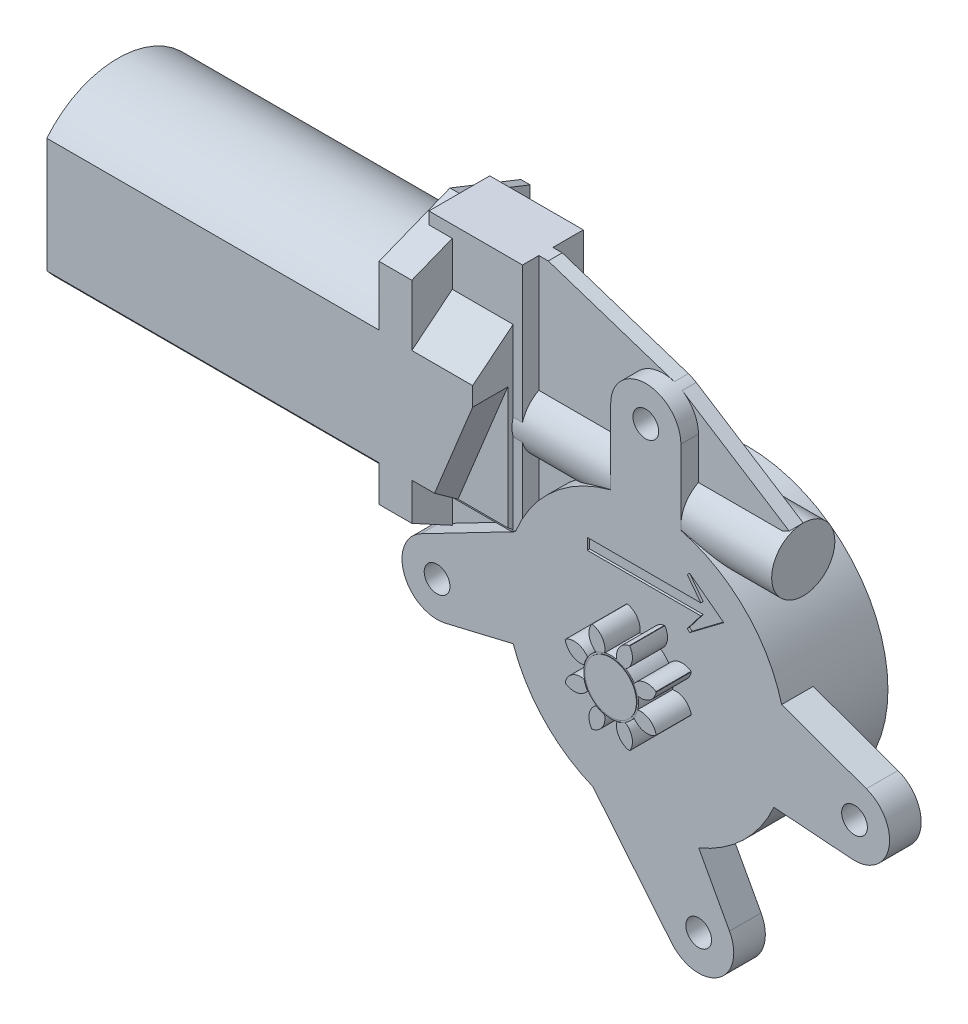
SolidWorks part; units mm, degrees
ref_plane "正面" through (0, 0, 0) normal (0, 0, 1) x (1, 0, 0)
ref_plane "平面" through (0, 0, 0) normal (0, 1, 0) x (1, 0, 0)
ref_plane "右側面" through (0, 0, 0) normal (1, 0, 0) x (0, 0, -1)
sketch "ｽｹｯﾁ2" plane through (0, 0, 0) normal (1, 0, 0) x (0, 0, -1)
  line L0 (0, 0) -> (0, 50000) construction
  line L1 (15.15, 12.2771) -> (15.15, -12.2771)
  line L2 (-15.15, 12.2771) -> (-15.15, -12.2771)
  arc A0 (-15.15, -12.2771) -> (15.15, -12.2771) centre (0, 0) ccw
  arc A2 (15.15, 12.2771) -> (-15.15, 12.2771) centre (0, 0) ccw
  dimension "D1" = 39
  dimension "D2" = 30.3
extrude "ﾎﾞｽ - 押し出し1" add sketch "ｽｹｯﾁ2" against normal blind 71
sketch "ｽｹｯﾁ3" plane through (-71, 0, 0) normal (-1, 0, 0) x (0, 0, 1)
  circle A0 centre (0, 0) radius 7
  dimension "D1" = 14
extrude "ﾎﾞｽ - 押し出し2" add sketch "ｽｹｯﾁ3" along normal blind 0.8
sketch "ｽｹｯﾁ4" plane through (-71.8, 0, 0) normal (-1, 0, 0) x (0, 0, 1)
  circle A0 centre (0, 0) radius 2.25
  dimension "D1" = 4.5
extrude "ﾎﾞｽ - 押し出し3" add sketch "ｽｹｯﾁ4" along normal blind 0.2
sketch "ｽｹｯﾁ5" plane through (0, 0, 0) normal (1, 0, 0) x (0, 0, -1)
  line L0 (0, 0) -> (0, 50000) construction
  line L1 (0, 0) -> (-50000, 0) construction
  line L2 (-15.15, 25) -> (-15.15, -20)
  line L3 (-15.15, -20) -> (5.15, -31)
  line L4 (5.15, -31) -> (15.15, -31)
  line L5 (15.15, -31) -> (15.15, 25)
  line L6 (15.15, 25) -> (0, 31)
  line L7 (0, 31) -> (-15.15, 25)
  line L8 (15.15, -12.2771) -> (15.15, 12.2771) construction
  line L9 (-15.15, 12.2771) -> (-15.15, -12.2771) construction
  circle A0 centre (0, 0) radius 26 construction
  circle A1 centre (0, 26) radius 2.5
  circle A2 centre (-10, 24) radius 2
  circle A3 centre (10, 24) radius 2
  circle A4 centre (7, -25.04) radius 2
  dimension "D6" = 52
  dimension "D8" = 5
  dimension "D9" = 4
  dimension "D10" = 7
  dimension "D11" = 4
  dimension "D2" = 31
  dimension "D3" = 25
  dimension "D4" = 62
  dimension "D5" = 20
  dimension "D7" = 10
  dimension "D12" = 10
extrude "ﾎﾞｽ - 押し出し4" add sketch "ｽｹｯﾁ5" along normal blind 2
sketch "ｽｹｯﾁ7" plane through (2, 0, 0) normal (1, 0, 0) x (0, 0, -1)
  circle A0 centre (0, 0) radius 6.75
  dimension "D1" = 13.5
extrude "ﾎﾞｽ - 押し出し7" add sketch "ｽｹｯﾁ7" along normal blind 73.5
sketch "ｽｹｯﾁ6" plane through (0, 0, 0) normal (0, 0, 1) x (1, 0, 0)
  line L0 (0, 0) -> (-50000, 0) construction
  line L1 (29.7505, -30) -> (-49970.2495, -30) construction
  line L2 (48.6, -30) -> (48.6, 49970) construction
  line L3 (2, 25) -> (2, -20) construction
  circle A0 centre (48.6, -30) radius 30
  dimension "D1" = 30
  dimension "D2" = 46.6
extrude "ﾎﾞｽ - 押し出し8" add sketch "ｽｹｯﾁ6" against normal blind 15
sketch "ｽｹｯﾁ8" plane through (0, 0, 0) normal (0, 0, 1) x (1, 0, 0)
  line L0 (48.6, -30) -> (48.6, 49970) construction
  line L1 (48.6, -30) -> (-49951.4, -30) construction
  line L2 (48.6, -36) -> (-49951.4, -36) construction
  line L3 (59.9, -30) -> (59.9, 49970) construction
  line L4 (54.1031, -78.2588) -> (37.3, -57.7905)
  line L5 (66.4901, -69.9194) -> (59.9, -57.7905)
  line L6 (92.6469, -43.4796) -> (75.9861, -42.2476)
  line L7 (95.741, -28.9436) -> (77.6268, -22.4207)
  line L8 (41.1, 15) -> (41.1, -0.9526)
  line L9 (56.1, 15) -> (56.1, -0.9526)
  line L10 (0.5475, -29.3419) -> (20.7407, -18.8709)
  line L11 (5.7319, -43.2973) -> (20.2627, -39.8487)
  arc A0 (41.1, -0.9526) -> (20.7407, -18.8709) centre (48.6, -30) ccw
  circle A1 centre (48.6, 15) radius 2.75
  circle A2 centre (4, -36) radius 2.75
  circle A3 centre (93.2, -36) radius 2.75
  circle A4 centre (59.9, -73.5) radius 2.75
  arc A5 (0.5475, -29.3419) -> (5.7319, -43.2973) centre (4, -36) ccw
  arc A6 (56.1, 15) -> (41.1, 15) centre (48.6, 15) ccw
  arc A7 (92.6469, -43.4796) -> (95.741, -28.9436) centre (93.2, -36) ccw
  arc A8 (54.1031, -78.2588) -> (66.4901, -69.9194) centre (59.9, -73.5) ccw
  arc A9 (29.6412, -6.75) -> (67.5588, -6.75) centre (48.6, -30) ccw construction
  arc A10 (59.9, -57.7905) -> (75.9861, -42.2476) centre (48.6, -30) ccw
  arc A11 (20.2627, -39.8487) -> (37.3, -57.7905) centre (48.6, -30) ccw
  arc A12 (77.6268, -22.4207) -> (56.1, -0.9526) centre (48.6, -30) ccw
  dimension "D3" = 60
  dimension "D4" = 43.5
  dimension "D5" = 44.6
  dimension "D6" = 44.6
  dimension "D8" = 5.5
  dimension "D9" = 15
  dimension "D1" = 11.3
  dimension "D2" = 6
  dimension "D7" = 45
extrude "ﾎﾞｽ - 押し出し9" add sketch "ｽｹｯﾁ8" along normal blind 6.75
sketch "ｽｹｯﾁ9" plane through (0, 0, 0) normal (0, 0, 1) x (1, 0, 0)
  line L0 (75.5, 6.75) -> (52.6308, 21.3247)
  line L1 (50.9466, 22.1235) -> (24, 31)
  line L2 (24, 31) -> (2, 31)
  line L3 (2, 31) -> (2, -28.5887)
  line L4 (20.7407, -18.8709) -> (0.5475, -29.3419) construction
  line L5 (2, -20) -> (2, -31) construction
  line L6 (2, -28.5887) -> (75.5, 6.75)
  arc A0 (56.1, 15) -> (41.1, 15) centre (48.6, 15) ccw construction
  arc A1 (50.9466, 22.1235) -> (52.6308, 21.3247) centre (48.6, 15) cw
  circle A2 centre (48.6, 15) radius 2.75
  dimension "D2" = 5.5
  dimension "D1" = 22
extrude "ﾎﾞｽ - 押し出し10" add sketch "ｽｹｯﾁ9" along normal blind 3 contours A1 L1 L2 L3 L6 L0 region at (28.0225, 5.7047, 0)
sketch "ｽｹｯﾁ10" plane through (0, 0, 0) normal (0, 0, 1) x (1, 0, 0)
  line L0 (2, 31) -> (22, 31)
  line L1 (24, 31) -> (2, 31) construction
  line L2 (22, 31) -> (22, -19.5)
  line L3 (22, -19.5) -> (2, -19.5)
  line L4 (2, 25) -> (2, -20) construction
  line L5 (2, -6.0467) -> (2, -26.5837) construction
  line L6 (-71, -19.5) -> (0, -19.5) construction
  line L7 (2, 31) -> (2, -19.5)
  dimension "D1" = 20
extrude "ﾎﾞｽ - 押し出し11" add sketch "ｽｹｯﾁ10" against normal blind 6.5 and the other way blind 6.5
sketch "ｽｹｯﾁ12" plane through (2, 0, 0) normal (1, 0, 0) x (0, 0, -1)
  line L0 (0, 0) -> (-50000, 0) construction
  line L1 (-15.15, 12) -> (-6.5, 19)
  line L2 (-15.15, 25) -> (-15.15, -20) construction
  line L4 (-6.5, 28.4257) -> (-6.5, 1.82) construction
  line L5 (-15.15, 12) -> (-15.15, -12)
  line L6 (-15.15, -12) -> (-6.5, -19)
  line L7 (-6.5, 19) -> (-6.5, -19)
  arc A0 (-6.5, 1.82) -> (-6.5, -1.82) centre (0, 0) ccw construction
  point P15 (-15.15, 0)
  point P16 (-6.75, 0)
  dimension "D1" = 24
  dimension "D2" = 38
extrude "ﾎﾞｽ - 押し出し19" add sketch "ｽｹｯﾁ12" along normal blind 18
sketch "ｽｹｯﾁ13" plane through (0, 0, 6.75) normal (0, 0, 1) x (1, 0, 0)
  circle A0 centre (48.6, -30) radius 10.5
  dimension "D1" = 21
extrude "ﾎﾞｽ - 押し出し20" add sketch "ｽｹｯﾁ13" along normal blind 7.5
sketch "ｽｹｯﾁ14" plane through (0, 0, 14.25) normal (0, 0, 1) x (1, 0, 0)
  circle A0 centre (48.6, -30) radius 5.85
  circle A1 centre (48.6, -30) radius 5.5
  dimension "D1" = 11
  dimension "D2" = 11.7
extrude "ｶｯﾄ - 押し出し1" cut sketch "ｽｹｯﾁ14" against normal blind 0.1
sketch "ｽｹｯﾁ15" plane through (0, 0, 15.15) normal (0, 0, 1) x (1, 0, 0)
  line L0 (0, 0) -> (-50000, 0) construction
  line L1 (2, 13.5772) -> (2, 50013.5772) construction
  line L3 (20, 8) -> (9, -19)
  line L4 (20, 1.82) -> (20, 19) construction
  line L5 (20, -19) -> (2, -19) construction
  line L6 (9, -19) -> (20, -19)
  line L7 (20, -19) -> (20, 8)
  dimension "D1" = 27
  dimension "D2" = 11
extrude "ｶｯﾄ - 押し出し2" cut sketch "ｽｹｯﾁ15" against normal blind 7.5
sketch "ｽｹｯﾁ16" plane through (2, 0, 0) normal (1, 0, 0) x (0, 0, -1)
  line L0 (-6.5, 28.4257) -> (-15.15, 25)
  line L1 (-15.15, 25) -> (-15.15, -20)
  line L2 (-15.15, -20) -> (-6.5, -24.6872)
  line L3 (-6.5, -24.6872) -> (-6.5, 28.4257)
  line L4 (-15.15, -20) -> (-3, -26.5837) construction
extrude "ﾎﾞｽ - 押し出し23" add sketch "ｽｹｯﾁ16" along normal blind 5
sketch "ｽｹｯﾁ17" plane through (0, 0, 6.75) normal (0, 0, 1) x (1, 0, 0)
  line L0 (48.6, -30) -> (48.6, -50030) construction
  line L1 (48.6, -30) -> (50048.6, -30) construction
  text T0 "→" font "MS UI Gothic" height in points 72
extrude "ｶｯﾄ - 押し出し3" cut sketch "ｽｹｯﾁ17" against normal blind 0.5
sketch "ｽｹｯﾁ18" plane through (0, 0, 14.25) normal (0, 0, 1) x (1, 0, 0)
  line L0 (48.6, -30) -> (50048.6, -30) construction
  line L1 (48.6, -30) -> (48.6, -50030) construction
  line L2 (42.9102, -16.2637) -> (19177.0818, -46210.2403) construction
  line L3 (110.94, -18.2904) -> (113.04, -18.2904) construction
  line L4 (110.94, -18.2904) -> (127.5765, -20.6285) construction
  line L5 (110.94, -18.2904) -> (110.873, -18.2904) construction
  line L6 (110.94, -18.2904) -> (110.8298, -18.3305) construction
  line L7 (46.8443, -21.7855) -> (45.4386, -22.3678) construction
  circle A0 centre (48.6, -30) radius 5.775 construction
  circle A1 centre (48.6, -30) radius 10.5 construction
  circle A2 centre (48.6, -30) radius 7.8934 construction
  circle A3 centre (48.6, -30) radius 8.4 construction
  arc A4 (44.628, -20.2803) -> (47.2686, -24.3806) centre (44.0049, -23.582) cw
  arc A5 (49.9314, -24.3806) -> (47.2686, -24.3806) centre (48.6, -30) ccw
  arc A6 (44.628, -20.2803) -> (52.572, -20.2803) centre (48.6, -30) cw
  arc A7 (52.572, -20.2803) -> (49.9314, -24.3806) centre (53.1951, -23.582) ccw
  circle M1 centre (48.6, -30) radius 5.85
  circle M2 centre (48.6, -30) radius 10.5
  dimension "D2" = 11.55
  dimension "D3" = 15.7868
  dimension "D4" = 21
  dimension "D5" = 16.8
  dimension "D6" = 3.36
  dimension "Ap" = 20
  dimension "Backlash" = 0.067
  dimension "m" = 2.1
  dimension "z" = 8
  dimension "d" = 16.8
  dimension "bl" = 0.1173
  dimension "D1" = 22.5
  dimension "D7" = 1.5215
extrude "ｶｯﾄ - 押し出し4" cut sketch "ｽｹｯﾁ18" against normal blind 7.5 contours A7 A4 M2 M1 region at (48.6, -21.4297, 14.25)
ref_plane "平面1" through (0, -30, 0) normal (0, 1, 0) x (-1, 0, 0)
sketch "ｽｹｯﾁ19" plane through (0, -30, 0) normal (0, 1, 0) x (-1, 0, 0)
  line L2 (-48.6, -7.5) -> (-48.6, 49992.5) construction
ref_axis "軸1" through (48.6, -30, -7.5) along (0, 0, 1)
pattern_circular "円形ﾊﾟﾀｰﾝ1" count 8 over 360 about axis through (48.6, -30, -7.5) along (0, 0, 1) of "ｶｯﾄ - 押し出し4"
ref_plane "平面2" through (0, 0, 15.15) normal (0, 0, 1) x (1, 0, 0)
equation "\"bl@ｽｹｯﾁ18\" = \"Backlash@ｽｹｯﾁ18\"*7/4"
equation "\"d@ｽｹｯﾁ18\" = \"m@ｽｹｯﾁ18\"*\"z@ｽｹｯﾁ18\""
equation "\"D1@ｽｹｯﾁ18\" = 180/\"z@ｽｹｯﾁ18\""
equation "\"D2@ｽｹｯﾁ18\" = \"d@ｽｹｯﾁ18\"-2.5*\"m@ｽｹｯﾁ18\""
equation "\"D3@ｽｹｯﾁ18\" = \"d@ｽｹｯﾁ18\" *cos( \"Ap@ｽｹｯﾁ18\"* pi /180 ) "
equation "\"D4@ｽｹｯﾁ18\" = \"d@ｽｹｯﾁ18\"+2*\"m@ｽｹｯﾁ18\""
equation "\"D5@ｽｹｯﾁ18\" = \"d@ｽｹｯﾁ18\""
equation "\"D6@ｽｹｯﾁ18\" = \"d@ｽｹｯﾁ18\"/5"
equation "\"D7@ｽｹｯﾁ18\" = \"d@ｽｹｯﾁ18\"* sin(  pi /2/\"z@ｽｹｯﾁ18\" )/2 -\"bl@ｽｹｯﾁ18\""
